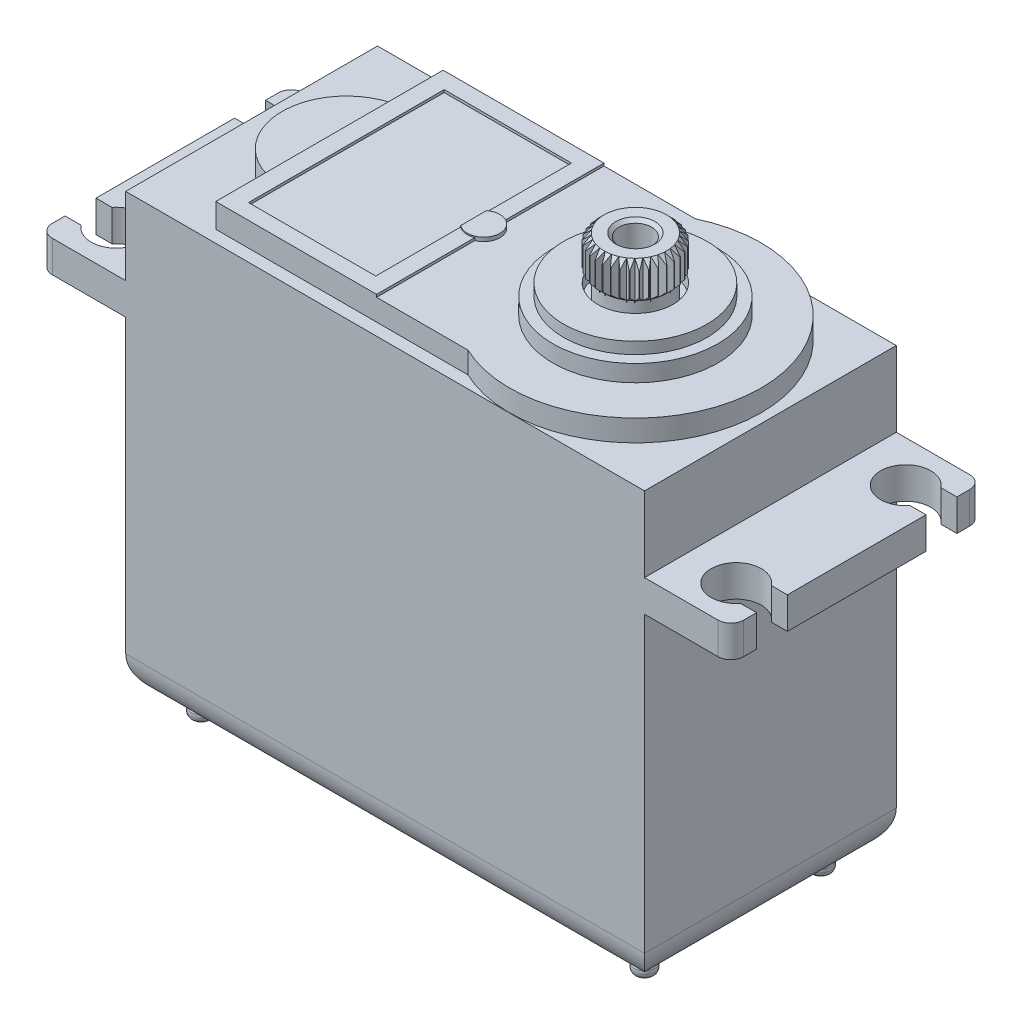
SolidWorks part; units mm, degrees
ref_plane "Front Plane" through (0, 0, 0) normal (0, 0, 1) x (1, 0, 0)
ref_plane "Top Plane" through (0, 0, 0) normal (0, 1, 0) x (1, 0, 0)
ref_plane "Right Plane" through (0, 0, 0) normal (1, 0, 0) x (0, 0, -1)
sketch "Sketch1" plane through (0, 0, 0) normal (0, 1, 0) x (1, 0, 0)
  line L1 (-18.6567, 11.3793) -> (21.6633, 11.3793)
  line L2 (-18.6567, 11.3793) -> (-18.6567, -8.1907)
  line L3 (-18.6567, -8.1907) -> (21.6633, -8.1907)
  line L4 (21.6633, 11.3793) -> (21.6633, -8.1907)
extrude "Boss-Extrude1" add sketch "Sketch1" along normal blind 35.37
sketch "Sketch2" plane through (21.6633, 0, 0) normal (1, 0, 0) x (0, 0, -1)
  line L0 (-8.1907, 0) -> (-8.1907, 3)
  line L1 (-8.1907, 35.37) -> (-8.1907, 0) construction
  line L2 (-8.1907, 3) -> (-5.1907, 0)
  line L3 (-8.1907, 0) -> (11.3793, 0) construction
  line L4 (-5.1907, 0) -> (-8.1907, 0)
  line L5 (1.5943, 0) -> (1.5943, 35.37) construction
  line L6 (-8.1907, 35.37) -> (11.3793, 35.37) construction
  line L7 (8.3793, 0) -> (11.3793, 0)
  line L8 (11.3793, 3) -> (8.3793, 0)
  line L9 (11.3793, 0) -> (11.3793, 3)
extrude "Cut-Extrude1" cut sketch "Sketch2" against normal up to next
sketch "Sketch3" plane through (0, 0, 8.1907) normal (0, 0, 1) x (1, 0, 0)
  line L0 (21.6633, 0) -> (18.6633, 0)
  line L1 (-18.6567, 0) -> (21.6633, 0) construction
  line L2 (18.6633, 0) -> (21.6633, 3)
  line L3 (21.6633, 35.37) -> (21.6633, 3) construction
  line L4 (21.6633, 3) -> (21.6633, 0)
  line L5 (1.5033, 35.37) -> (1.5033, 0) construction
  line L6 (-18.6567, 35.37) -> (21.6633, 35.37) construction
  line L7 (-18.6567, 3) -> (-18.6567, 0)
  line L8 (-15.6567, 0) -> (-18.6567, 3)
  line L9 (-18.6567, 0) -> (-15.6567, 0)
extrude "Cut-Extrude2" cut sketch "Sketch3" against normal up to next
fillet "Fillet2" radius 3 4 edges at (21.6633, 3, -1.5943) (1.5033, 3, 8.1907) (-18.6567, 3, -1.5943) (1.5033, 3, -11.3793)
sketch "Sketch5" plane through (21.6633, 0, 0) normal (1, 0, 0) x (0, 0, -1)
  line L0 (1.5943, 35.37) -> (1.5943, 29.53) construction
  line L1 (-8.1907, 35.37) -> (11.3793, 35.37) construction
  line L2 (-8.1907, 29.53) -> (1.5943, 29.53)
  line L3 (-8.1907, 35.37) -> (-8.1907, 4.2426) construction
  line L4 (1.5943, 29.53) -> (11.3793, 29.53)
  line L5 (11.3793, 35.37) -> (11.3793, 4.2426) construction
  line L6 (11.3793, 29.53) -> (11.3793, 27.07)
  line L7 (11.3793, 27.07) -> (-8.1907, 27.07)
  line L8 (-8.1907, 27.07) -> (-8.1907, 29.53)
extrude "Boss-Extrude2" add sketch "Sketch5" along normal blind 6.71
sketch "Sketch7" plane through (-18.6567, 0, 0) normal (-1, 0, 0) x (0, 0, 1)
  line L0 (-1.5943, 35.37) -> (-1.5943, 29.3613) construction
  line L1 (-11.3793, 29.3613) -> (-1.5943, 29.3613)
  line L2 (-1.5943, 29.3613) -> (8.1907, 29.3613)
  line L3 (8.1907, 29.3613) -> (8.1907, 26.9013)
  line L4 (8.1907, 26.9013) -> (-11.3793, 26.9013)
  line L5 (-11.3793, 26.9013) -> (-11.3793, 29.3613)
  line L6 (-11.3793, 35.37) -> (8.1907, 35.37) construction
  line L7 (8.1907, 35.37) -> (8.1907, 4.2426) construction
  line L8 (-11.3793, 35.37) -> (-11.3793, 4.2426) construction
extrude "Boss-Extrude3" add sketch "Sketch7" along normal blind 6.71
sketch "Sketch8" plane through (0, 29.53, 0) normal (0, 1, 0) x (1, 0, 0)
  line L0 (28.3733, 1.5943) -> (-25.3667, 1.5943) construction
  line L2 (-25.3667, -8.1907) -> (-25.3667, 11.3793) construction
  line L4 (28.3733, -3.7925) -> (27.1303, -3.7925)
  line L5 (28.3733, 11.3793) -> (28.3733, -8.1907) construction
  line L6 (28.3733, 8.181) -> (28.3733, 9.381)
  line L7 (28.3733, 9.381) -> (27.1303, 9.381)
  line L8 (28.3733, 8.181) -> (28.3733, 6.981)
  line L9 (28.3733, 6.981) -> (27.1303, 6.981)
  line L10 (28.3733, -4.9925) -> (28.3733, -3.7925)
  line L11 (28.3733, -6.1925) -> (27.1303, -6.1925)
  line L12 (28.3733, -4.9925) -> (28.3733, -6.1925)
  line L13 (1.5033, 11.3793) -> (1.5033, -8.1907) construction
  line L14 (21.6633, 11.3793) -> (-18.6567, 11.3793) construction
  line L15 (-18.6567, -8.1907) -> (21.6633, -8.1907) construction
  line L24 (-25.3667, 6.981) -> (-24.1237, 6.981)
  line L25 (-25.3667, -4.9925) -> (-25.3667, -6.1925)
  line L26 (-25.3667, -6.1925) -> (-24.1237, -6.1925)
  line L27 (-25.3667, -4.9925) -> (-25.3667, -3.7925)
  line L28 (-25.3667, -3.7925) -> (-24.1237, -3.7925)
  line L29 (-25.3667, 8.181) -> (-25.3667, 6.981)
  line L30 (-25.3667, 9.381) -> (-24.1237, 9.381)
  line L31 (-25.3667, 8.181) -> (-25.3667, 9.381)
  arc A0 (27.1303, -3.7925) -> (27.1303, -6.1925) centre (25.5933, -4.9925) ccw
  arc A1 (27.1303, 6.981) -> (27.1303, 9.381) centre (25.5933, 8.181) cw
  arc A4 (-24.1237, 6.981) -> (-24.1237, 9.381) centre (-22.5867, 8.181) ccw
  arc A5 (-24.1237, -3.7925) -> (-24.1237, -6.1925) centre (-22.5867, -4.9925) cw
extrude "Cut-Extrude3" cut sketch "Sketch8" against normal up to next
sketch "Sketch9" plane through (0, 35.37, 0) normal (0, 1, 0) x (1, 0, 0)
  line L0 (6.9933, -8.1907) -> (6.9933, -7.2426) construction
  line L1 (-18.6567, 6.4311) -> (-12.6067, 6.4311) construction
  line L2 (6.9933, 11.3793) -> (6.9933, 10.4311) construction
  line L3 (-18.6567, -3.2426) -> (-12.6067, -3.2426) construction
  line L4 (-18.6567, -8.1907) -> (-18.6567, 11.3793) construction
  line L5 (-18.6567, 1.5943) -> (21.6633, 1.5943) construction
  line L6 (-12.6067, 10.4311) -> (6.9933, 10.4311)
  line L7 (-18.6567, 11.3793) -> (-18.6567, -8.1907) construction
  line L8 (-12.6067, -7.2426) -> (-12.6067, -3.2426)
  line L9 (21.6633, -8.1907) -> (21.6633, 11.3793) construction
  line L10 (-12.6067, 10.4311) -> (-12.6067, 6.4311)
  line L11 (-12.6067, -7.2426) -> (6.9933, -7.2426)
  line L12 (21.6633, 1.5943) -> (20.9438, 1.5943) construction
  line L13 (21.6633, 11.3793) -> (-18.6567, 11.3793) construction
  arc A0 (6.9933, 10.4311) -> (6.9933, -7.2426) centre (11.1697, 1.5943) cw
  arc A1 (-12.6067, 6.4311) -> (-12.6067, -3.2426) centre (-11.2767, 1.5943) ccw
extrude "Boss-Extrude4" add sketch "Sketch9" along normal blind 1.67
sketch "Sketch10" plane through (0, 37.04, 0) normal (0, 1, 0) x (1, 0, 0)
  circle A1 centre (11.1697, 1.5943) radius 6.415
extrude "Boss-Extrude5" add sketch "Sketch10" along normal blind 1.3
sketch "Sketch11" plane through (0, 38.34, 0) normal (0, 1, 0) x (-1, 0, 0)
  circle A2 centre (-11.1697, -1.5943) radius 5.575
extrude "Boss-Extrude6" add sketch "Sketch11" along normal blind 0.9
sketch "Sketch12" plane through (0, 39.24, 0) normal (0, 1, 0) x (1, 0, 0)
  circle A1 centre (11.1697, 1.5943) radius 2.925
extrude "Cut-Extrude4" cut sketch "Sketch12" against normal blind 1
sketch "Sketch13" plane through (0, 38.24, 0) normal (0, 1, 0) x (-1, 0, 0)
  circle A0 centre (-11.1697, -1.5943) radius 2.425
extrude "Boss-Extrude7" add sketch "Sketch13" along normal blind 1.5
sketch "Sketch14" plane through (0, 39.74, 0) normal (0, 1, 0) x (1, 0, 0)
  circle A0 centre (11.1697, 1.5943) radius 2.925
extrude "Boss-Extrude8" add sketch "Sketch14" along normal blind 2.86
sketch "Sketch15" plane through (0, 42.6, 0) normal (0, 1, 0) x (1, 0, 0)
  circle A0 centre (11.1697, 1.5943) radius 1.27
extrude "Cut-Extrude5" cut sketch "Sketch15" against normal blind 7
sketch "Sketch16" plane through (0, 37.04, 0) normal (0, 1, 0) x (1, 0, 0)
  line L0 (-12.6067, -7.2426) -> (6.9933, -7.2426) construction
  line L1 (-12.6067, 10.4311) -> (-0.1067, 10.4311)
  line L2 (-12.6067, 10.4311) -> (-12.6067, -7.2426)
  line L3 (-12.6067, -7.2426) -> (-0.1067, -7.2426)
  line L4 (-0.1067, 10.4311) -> (-0.1067, -7.2426)
  line L5 (-6.3168, 9.1673) -> (-6.3567, 10.4311) construction
  line L6 (-11.2628, 9.1673) -> (-1.3708, 9.1673)
  line L7 (-11.2628, 9.1673) -> (-11.2628, -6.0433)
  line L8 (-11.2628, -6.0433) -> (-1.3708, -6.0433)
  line L9 (-1.3708, 9.1673) -> (-1.3708, 1.562)
  line L10 (-11.2628, 1.562) -> (-12.6067, 1.5943) construction
  line L11 (-1.3708, 1.562) -> (-0.1067, 1.5943) construction
  line L12 (-6.3168, -6.0433) -> (-6.3567, -7.2426) construction
  line L13 (-1.3708, 1.562) -> (-1.3708, -6.0433)
extrude "Boss-Extrude9" add sketch "Sketch16" along normal blind 0.2
sketch "Sketch17" plane through (0, 37.24, 0) normal (0, 1, 0) x (-1, 0, 0)
  line L0 (1.3708, -1.562) -> (1.3708, -2.562)
  line L1 (1.3708, 6.0433) -> (1.3708, -9.1673) construction
  line L2 (1.3708, -1.562) -> (1.3708, -0.562)
  arc A0 (1.3708, -2.562) -> (1.3708, -0.562) centre (0.592, -1.562) cw
extrude "Boss-Extrude10" add sketch "Sketch17" along normal blind 0.1 and the other way blind 0.5
sketch "Sketch19" plane through (0, 42.6, 0) normal (0, 1, 0) x (1, 0, 0)
  line L0 (10.8404, 4.5007) -> (11.3402, 4.5143) construction
  line L1 (11.3402, 4.5143) -> (11.0903, 4.0075)
  line L2 (11.0903, 4.0075) -> (10.8404, 4.5007)
  line L3 (11.0903, 4.5075) -> (11.0903, 4.0075) construction
  line L4 (10.8404, 4.5007) -> (10.7613, 4.6463)
  line L5 (11.3402, 4.5143) -> (11.4053, 4.6463)
  line L6 (10.7613, 4.6463) -> (11.4053, 4.6463)
  circle A3 centre (11.1697, 1.5943) radius 2.925 construction
  circle A4 centre (11.1697, 1.5943) radius 2.925 construction
extrude "Cut-Extrude11" cut sketch "Sketch19" against normal blind 3
sketch "Sketch21" plane through (0, 0, 0) normal (0, -1, 0) x (1, 0, 0)
  line L0 (1.5033, 5.1907) -> (1.5033, -8.3793) construction
  line L1 (20.7846, 7.3121) -> (17.7846, 7.3121)
  line L2 (20.7846, 7.3121) -> (20.7846, 4.3121)
  line L3 (20.7846, 4.3121) -> (17.7846, 4.3121)
  line L4 (17.7846, 7.3121) -> (17.7846, 4.3121)
  line L5 (-15.6567, 5.1907) -> (18.6633, 5.1907) construction
  line L6 (-15.6567, -8.3793) -> (18.6633, -8.3793) construction
  line L7 (-15.6567, -1.5943) -> (18.6633, -1.5943) construction
  line L8 (-15.6567, -8.3793) -> (-15.6567, 5.1907) construction
  line L9 (18.6633, -8.3793) -> (18.6633, 5.1907) construction
  line L10 (17.7846, -10.5006) -> (17.7846, -7.5006)
  line L11 (20.7846, -7.5006) -> (17.7846, -7.5006)
  line L12 (20.7846, -10.5006) -> (20.7846, -7.5006)
  line L13 (20.7846, -10.5006) -> (17.7846, -10.5006)
  line L14 (-17.778, -7.5006) -> (-14.778, -7.5006)
  line L15 (-14.778, -10.5006) -> (-14.778, -7.5006)
  line L16 (-14.778, 7.3121) -> (-14.778, 4.3121)
  line L17 (-17.778, 4.3121) -> (-14.778, 4.3121)
  line L18 (-17.778, -10.5006) -> (-14.778, -10.5006)
  line L19 (-17.778, -10.5006) -> (-17.778, -7.5006)
  line L20 (-17.778, 7.3121) -> (-17.778, 4.3121)
  line L21 (-17.778, 7.3121) -> (-14.778, 7.3121)
extrude "Cut-Extrude12" cut sketch "Sketch21" against normal blind 1
fillet "Fillet4" radius 1 4 edges at (-14.778, 0.5, -7.5006) (-14.778, 0.5, 4.3121) (17.7846, 0.5, -7.5006) (17.7846, 0.5, 4.3121)
fillet "Fillet5" radius 1 4 edges at (-25.3667, 28.1313, 8.1907) (-25.3667, 28.1313, -11.3793) (28.3733, 28.3, -11.3793) (28.3733, 28.3, 8.1907)
chamfer "Chamfer2" distance 0.5 angle 45 2 edges at (11.2493, 42.6, 1.3297) (11.2493, 39.74, 1.3297)
chamfer "Chamfer3" distance 0.25 angle 45 1 edges at (11.1697, 42.6, -0.3243)
pattern_circular "CirPattern12" count 34 over 360 about axis through (11.1697, 0, -1.5943) along (0, 1, 0) of "Cut-Extrude11"
sketch "Sketch23" plane through (0, 1, 0) normal (0, -1, 0) x (1, 0, 0)
  line L0 (1.5033, 5.1907) -> (1.5033, -8.3793) construction
  line L1 (-14.7854, 5.1907) -> (17.792, 5.1907) construction
  line L2 (-14.7854, -8.3793) -> (17.792, -8.3793) construction
  line L3 (18.6633, -1.5943) -> (-15.6567, -1.5943) construction
  line L4 (18.6633, -7.508) -> (18.6633, 4.3195) construction
  line L5 (-15.6567, -7.508) -> (-15.6567, 4.3195) construction
  circle A0 centre (18.7344, -8.4503) radius 0.4237
  circle A1 centre (18.7344, 5.2618) radius 0.4237
  circle A2 centre (-15.7278, 5.2618) radius 0.4237
  circle A3 centre (-15.7278, -8.4503) radius 0.4237
extrude "Boss-Extrude12" add sketch "Sketch23" along normal blind 0.1
sketch "Sketch24" plane through (0, 0.9, 0) normal (0, -1, 0) x (1, 0, 0)
  line L0 (1.5033, 5.1907) -> (1.5033, -8.3793) construction
  line L1 (-14.7854, 5.1907) -> (17.792, 5.1907) construction
  line L2 (-14.7854, -8.3793) -> (17.792, -8.3793) construction
  line L3 (18.6633, -1.5943) -> (-15.6567, -1.5943) construction
  line L4 (18.6633, -7.508) -> (18.6633, 4.3195) construction
  line L5 (-15.6567, -7.508) -> (-15.6567, 4.3195) construction
  circle A0 centre (18.7344, -8.4503) radius 0.8
  circle A1 centre (18.7344, 5.2618) radius 0.8
  circle A2 centre (-15.7278, 5.2618) radius 0.8
  circle A3 centre (-15.7278, -8.4503) radius 0.8
extrude "Boss-Extrude13" add sketch "Sketch24" along normal blind 0.9
fillet "Fillet8" radius 0.45 4 edges at (18.7344, 0, -9.2503) (-15.7278, 0, -7.6503) (-15.7278, 0, 4.4618) (18.7344, 0, 6.0618)
fillet "Fillet9" radius 0.2 4 edges at (-15.7278, 0.9, -7.6503) (-15.7278, 0.9, 4.4618) (18.7344, 0.9, 6.0618) (18.7344, 0.9, -9.2503)
sketch "Sketch25" plane through (0, 0, 0) normal (0, -1, 0) x (1, 0, 0)
  line L0 (18.0844, 5.3868) -> (18.0844, 5.1368)
  line L1 (18.6094, 4.6118) -> (18.8594, 4.6118)
  line L2 (18.0844, 5.3868) -> (18.6094, 5.3868)
  line L3 (18.6094, 5.3868) -> (18.6094, 5.9118)
  line L4 (19.3844, 5.1368) -> (19.3844, 5.3868)
  line L5 (18.8594, 5.9118) -> (18.6094, 5.9118)
  line L6 (1.5033, 5.1907) -> (1.5033, -8.3793) construction
  line L7 (-14.7854, 5.1907) -> (17.792, 5.1907) construction
  line L8 (-14.7854, -8.3793) -> (17.792, -8.3793) construction
  line L9 (18.6633, -1.5943) -> (-15.6567, -1.5943) construction
  line L10 (18.6633, -7.508) -> (18.6633, 4.3195) construction
  line L11 (-15.6567, -7.508) -> (-15.6567, 4.3195) construction
  line L12 (18.6094, -8.3253) -> (18.0844, -8.3253)
  line L13 (18.6094, -7.8003) -> (18.6094, -8.3253)
  line L14 (18.8594, -8.3253) -> (18.8594, -7.8003)
  line L15 (19.3844, -8.3253) -> (18.8594, -8.3253)
  line L16 (18.8594, -8.5753) -> (19.3844, -8.5753)
  line L17 (18.8594, 5.9118) -> (18.8594, 5.3868)
  line L18 (18.8594, 5.3868) -> (19.3844, 5.3868)
  line L19 (18.8594, -9.1003) -> (18.8594, -8.5753)
  line L20 (19.3844, 5.1368) -> (18.8594, 5.1368)
  line L21 (18.8594, 5.1368) -> (18.8594, 4.6118)
  line L22 (18.8594, -9.1003) -> (18.6094, -9.1003)
  line L23 (18.6094, 4.6118) -> (18.6094, 5.1368)
  line L24 (18.6094, 5.1368) -> (18.0844, 5.1368)
  line L25 (19.3844, -8.3253) -> (19.3844, -8.5753)
  line L26 (18.6094, -8.5753) -> (18.6094, -9.1003)
  line L27 (18.0844, -8.5753) -> (18.6094, -8.5753)
  line L28 (18.6094, -7.8003) -> (18.8594, -7.8003)
  line L29 (18.0844, -8.5753) -> (18.0844, -8.3253)
  line L30 (-15.0778, -8.5753) -> (-15.0778, -8.3253)
  line L31 (-15.6028, -7.8003) -> (-15.8528, -7.8003)
  line L32 (-15.0778, -8.5753) -> (-15.6028, -8.5753)
  line L33 (-15.6028, -8.5753) -> (-15.6028, -9.1003)
  line L34 (-16.3778, -8.3253) -> (-16.3778, -8.5753)
  line L35 (-15.6028, 5.1368) -> (-15.0778, 5.1368)
  line L36 (-15.6028, 4.6118) -> (-15.6028, 5.1368)
  line L37 (-15.8528, -9.1003) -> (-15.6028, -9.1003)
  line L38 (-15.8528, 5.1368) -> (-15.8528, 4.6118)
  line L39 (-16.3778, 5.1368) -> (-15.8528, 5.1368)
  line L40 (-15.8528, -9.1003) -> (-15.8528, -8.5753)
  line L41 (-15.8528, 5.3868) -> (-16.3778, 5.3868)
  line L42 (-15.8528, 5.9118) -> (-15.8528, 5.3868)
  line L43 (-15.8528, -8.5753) -> (-16.3778, -8.5753)
  line L44 (-16.3778, -8.3253) -> (-15.8528, -8.3253)
  line L45 (-15.8528, -8.3253) -> (-15.8528, -7.8003)
  line L46 (-15.6028, -7.8003) -> (-15.6028, -8.3253)
  line L47 (-15.6028, -8.3253) -> (-15.0778, -8.3253)
  line L48 (-15.8528, 5.9118) -> (-15.6028, 5.9118)
  line L49 (-16.3778, 5.1368) -> (-16.3778, 5.3868)
  line L50 (-15.6028, 5.3868) -> (-15.6028, 5.9118)
  line L51 (-15.0778, 5.3868) -> (-15.6028, 5.3868)
  line L52 (-15.6028, 4.6118) -> (-15.8528, 4.6118)
  line L53 (-15.0778, 5.3868) -> (-15.0778, 5.1368)
extrude "Cut-Extrude14" cut sketch "Sketch25" against normal blind 0.6
move or copy body "Body-Move/Copy1" [suppressed] bodies to move or copy 132
